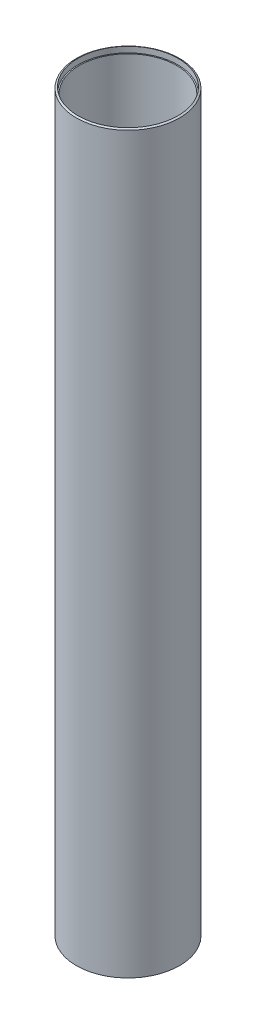
SolidWorks part; units mm, degrees
material "6061-T6 (SS)"
ref_plane "Front Plane" through (0, 0, 0) normal (0, 0, 1) x (1, 0, 0)
ref_plane "Top Plane" through (0, 0, 0) normal (0, 1, 0) x (1, 0, 0)
ref_plane "Right Plane" through (0, 0, 0) normal (1, 0, 0) x (0, 0, -1)
ref_axis "Axis1" through (0, 819.187, 0) along (0, -1, 0)
sketch "Sketch2" plane through (0, 0, 0) normal (0, 0, 1) x (1, 0, 0)
  line L0 (-57.15, 1.0999) -> (-57.15, 813.8999)
  line L1 (-55.245, 0) -> (-57.15, 1.0999)
  line L2 (-53.975, 6.35) -> (-53.975, 808.6497)
  line L3 (-55.245, 0) -> (-55.245, 6.35)
  line L4 (-57.15, 407.4999) -> (-53.086, 407.4999) construction
  line L5 (0, 819.187) -> (0, -55) construction
  line L6 (-55.245, 814.9997) -> (-57.15, 813.8999)
  line L7 (-55.245, 808.6497) -> (-53.975, 808.6497)
  line L8 (-55.245, 814.9997) -> (-55.245, 808.6497)
  line L9 (-55.245, 6.35) -> (-53.975, 6.35)
  line L13 (55, 0) -> (-55, 0) construction
  point P1 (-57.15, 407.4999)
  point P17 (-53.975, 407.4999)
  dimension "D2" = 3.175
  dimension "D3" = 406.4
  dimension "D4" = 57.15
  dimension "D6" = 60
  dimension "D10" = 1.27
  dimension "D11" = 6.35
revolve "Revolve1" add sketch "Sketch2" angle 360 about axis through (0, 819.187, 0) along (0, -1, 0)
